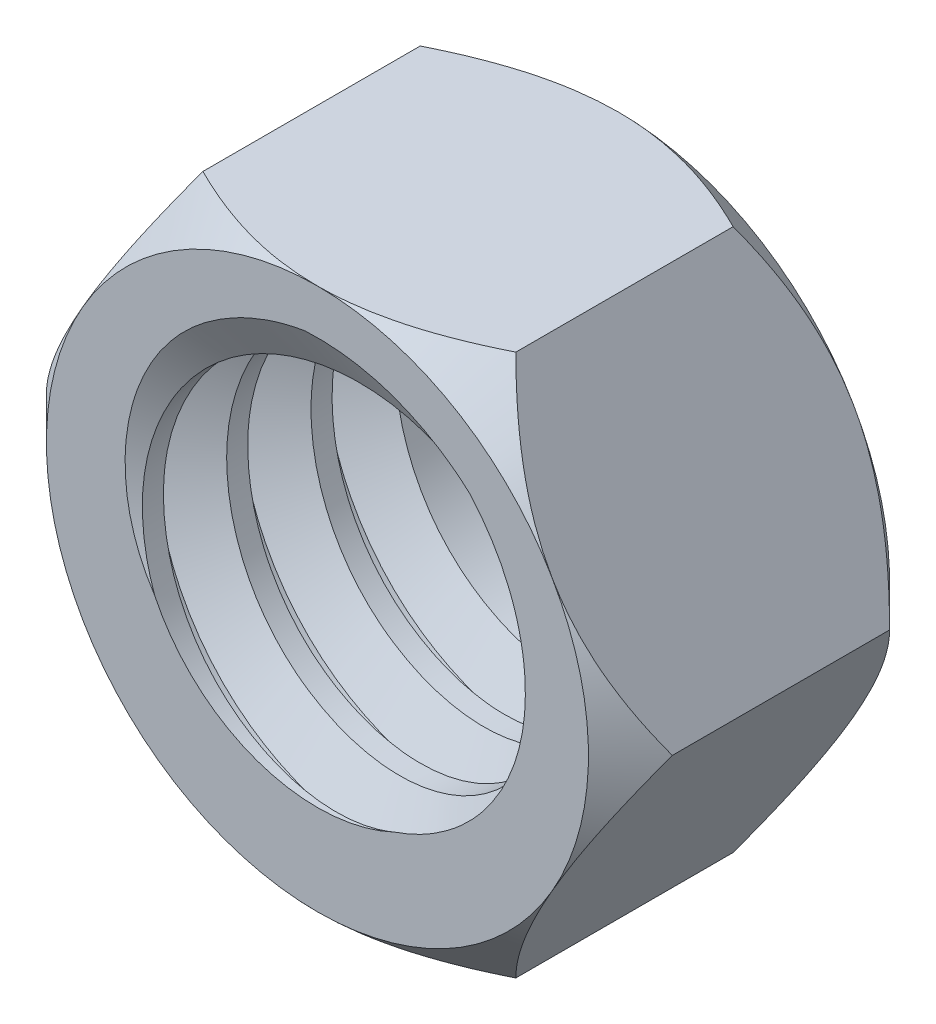
SolidWorks part; units mm, degrees
ref_plane "Front Plane" through (0, 0, 0) normal (0, 0, 1) x (1, 0, 0)
ref_plane "Top Plane" through (0, 0, 0) normal (0, 1, 0) x (1, 0, 0)
ref_plane "Right Plane" through (0, 0, 0) normal (1, 0, 0) x (0, 0, -1)
sketch "Sketch1" plane through (0, 0, 0) normal (0, 0, 1) x (1, 0, 0)
  line L0 (-2.5981, 0) -> (2.5981, 0) construction
  line L1 (2.5981, 0) -> (1.299, 2.25)
  line L2 (1.299, 2.25) -> (-1.299, 2.25)
  line L3 (-1.299, 2.25) -> (-2.5981, 0)
  line L4 (-2.5981, 0) -> (-1.299, -2.25)
  line L5 (-1.299, -2.25) -> (1.299, -2.25)
  line L6 (1.299, -2.25) -> (2.5981, 0)
  line L7 (0, -2.25) -> (0, 2.25) construction
  circle A0 centre (0, 0) radius 2.25
  circle A1 centre (0, 0) radius 1.5
  dimension "D1" = 4.5
  dimension "D2" = 3
extrude "Boss-Extrude1" add sketch "Sketch1" along normal blind 2.5 contours L3 L4 L5 L6 L1 L2
extrude "Cut-Extrude1" cut sketch "Sketch1<3>" along normal up to next contours A1
sketch "Sketch1<3>" plane through (0, 0, 0) normal (0, 0, 1) x (1, 0, 0) same geometry as "Sketch1"
extrude "Cut-Extrude2" cut sketch "Sketch1<4>" along normal blind 1 draft 45 flip side to cut contours A0
sketch "Sketch1<4>" plane through (0, 0, 0) normal (0, 0, 1) x (1, 0, 0) same geometry as "Sketch1"
ref_plane "Plane1" through (0, 0, 2.5) normal (0, 0, 1) x (1, 0, 0)
sketch "Sketch2" plane through (0, 0, 2.5) normal (0, 0, 1) x (1, 0, 0)
  circle A0 centre (0, 0) radius 2.25
  dimension "D1" = 4.5
extrude "Cut-Extrude3" cut sketch "Sketch2" against normal blind 1 draft 45 flip side to cut
thread "Thread1" pitch 0.7 method cut profile "Thread Profile1" start angle 0, offset 0, length 0, pitch 0.7, diameter 3
ref_plane "Plane2" through (1.5, 0, 0) normal (0, -1, 0) x (1, 0, 0)
sketch "Thread Profile1" plane through (1.5, 0, 0) normal (0, -1, 0) x (1, 0, 0)
  line L0 (0, 0) -> (0, 0.7) construction
  line L1 (0, 0) -> (0.3789, 0.2187)
  line L2 (0.3789, 0.2187) -> (0.3789, 0.3062)
  line L3 (0.3789, 0.3062) -> (0, 0.525)
  line L4 (0.3789, 0.2625) -> (0, 0.2625) construction
  line L11 (0, 0) -> (0, 0.525)
  point P2 (0, 0)
  dimension "Pitch" = 0.7
  dimension "Profile_Angle" = 60
  dimension "Profile_Land" = 0.0875
  dimension "Profile_Height" = 0.3789
